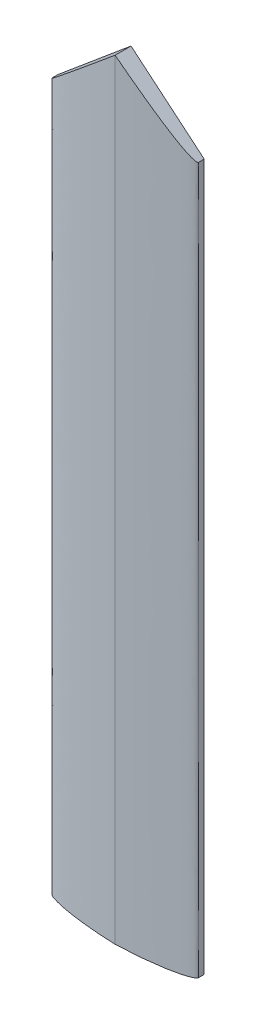
SolidWorks part; units mm, degrees
ref_plane "정면" through (0, 0, 0) normal (0, 0, 1) x (1, 0, 0)
ref_plane "윗면" through (0, 0, 0) normal (0, 1, 0) x (1, 0, 0)
ref_plane "우측면" through (0, 0, 0) normal (1, 0, 0) x (0, 0, -1)
sketch "스케치1" plane through (0, 0, 0) normal (0, 0, 1) x (1, 0, 0)
  line L0 (-13.25, 56.8461) -> (0, 67.9539)
  line L2 (-13.25, 56.8461) -> (-13.25, -70.9836)
  line L4 (13.25, 56.8461) -> (13.25, -70.9836)
  line L5 (-13.25, 56.8461) -> (16.486, -70.7296) construction
  line L6 (-16.486, -70.7296) -> (13.25, 56.8461) construction
  line L7 (0, 67.9539) -> (13.25, 56.8461)
  arc A0 (13.25, -70.9836) -> (-13.25, -70.9836) centre (0, 118.5539) cw
  point P0 (0, 0)
  point P10 (0, -71.4461)
  dimension "D2" = 190
  dimension "D1" = 26.5
  dimension "D3" = 139.4
  dimension "D4" = 17.29
extrude "보스-돌출1" add sketch "스케치1" along normal blind 3
fillet "필렛1" radius 2 2 edges at (-13.25, -7.0687, 3) (13.25, -7.0687, 3) second distance 20 first distance on face at (-13.25, -7.0687, 1.5) first distance on face at (13.25, -7.0687, 1.5)
